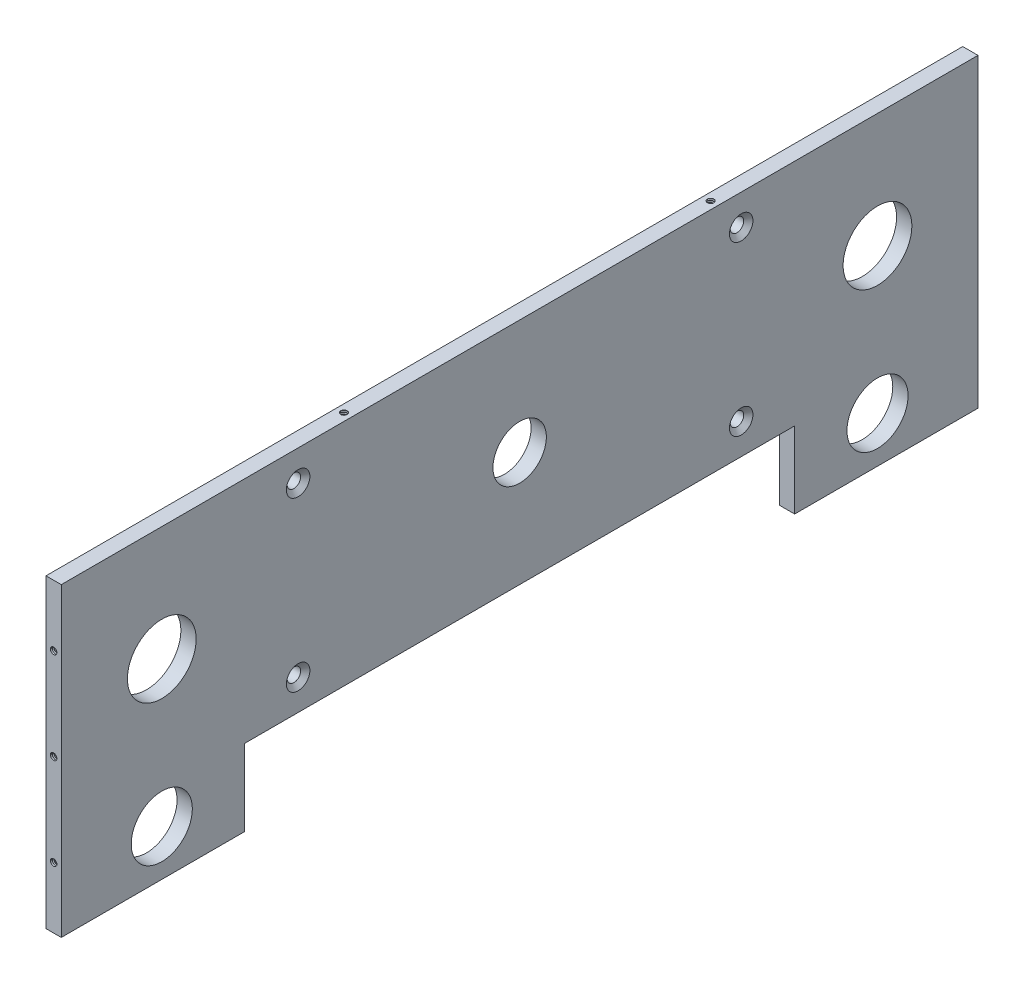
SolidWorks part; units mm, degrees
material "6061-T6 (SS)"
ref_plane "Front Plane" through (0, 0, 0) normal (0, 0, 1) x (1, 0, 0)
ref_plane "Top Plane" through (0, 0, 0) normal (0, 1, 0) x (1, 0, 0)
ref_plane "Right Plane" through (0, 0, 0) normal (1, 0, 0) x (0, 0, -1)
sketch "Sketch1" plane through (0, 0, 0) normal (1, 0, 0) x (0, 0, -1)
  line L1 (-190.5, 63.5) -> (190.5, 63.5)
  line L2 (-190.5, 63.5) -> (-190.5, -63.5)
  line L3 (-190.5, -63.5) -> (190.5, -63.5)
  line L4 (190.5, 63.5) -> (190.5, -63.5)
  line L5 (-190.5, 63.5) -> (190.5, -63.5) construction
  line L6 (-190.5, -63.5) -> (190.5, 63.5) construction
  point P0 (0, 0)
  dimension "D1" = 127
  dimension "D2" = 381
extrude "Boss-Extrude1" add sketch "Sketch1" along normal blind 6.35
sketch "Sketch2" plane through (6.35, 0, 0) normal (1, 0, 0) x (0, 0, -1)
  line L0 (-190.5, -63.5) -> (190.5, -63.5) construction
  line L1 (-148.7297, 15.875) -> (0, 15.875) construction
  line L2 (-74.3648, -34.925) -> (-74.3648, 15.875) construction
  line L3 (0, 15.875) -> (148.7297, 15.875) construction
  line L4 (74.3648, -34.925) -> (74.3648, 15.875) construction
  line L5 (190.5, 63.5) -> (-190.5, 63.5) construction
  line L6 (65.278, 53.34) -> (-56.642, 53.34) construction
  line L7 (65.278, 53.34) -> (65.278, -13.97) construction
  line L8 (65.278, -13.97) -> (-56.642, -13.97) construction
  line L9 (-56.642, 53.34) -> (-56.642, -13.97) construction
  line L10 (-190.5, -63.5) -> (190.5, -63.5) construction
  circle A1 centre (-148.7297, 15.875) radius 14.2875
  circle A2 centre (148.7297, 15.875) radius 14.2875
  circle A3 centre (-148.7297, 15.875) radius 38.1 construction
  circle A4 centre (0, 15.875) radius 38.1 construction
  circle A5 centre (148.7297, 15.875) radius 38.1 construction
  circle A6 centre (-74.3648, -34.925) radius 6.35 construction
  circle A7 centre (74.3648, -34.925) radius 6.35 construction
  circle A8 centre (-74.3648, 9.525) radius 6.35 construction
  circle A9 centre (74.3648, 9.525) radius 6.35 construction
  circle A11 centre (-148.7297, -44.4161) radius 12.7
  circle A12 centre (148.7297, -44.4161) radius 12.7
  circle A13 centre (0, 15.875) radius 11.1125
  point P11 (0, 0)
  dimension "D1" = 28.575
  dimension "D5" = 76.2
  dimension "D7" = 12.7
  dimension "D14" = 25.4
  dimension "D15" = 19.0839
  dimension "D17" = 25.4
  dimension "D20" = 22.225
  dimension "D21" = 28.575
  dimension "D2" = 79.375
  dimension "D3" = 148.7297
  dimension "D4" = 148.7297
  dimension "D6" = 0
  dimension "D8" = 28.575
  dimension "D9" = 44.45
  dimension "D10" = 56.642
  dimension "D11" = 121.92
  dimension "D12" = 10.16
  dimension "D13" = 49.53
  dimension "D16" = 148.7297
  dimension "D18" = 19.0839
  dimension "D19" = 148.7297
extrude "Cut-Extrude1" cut sketch "Sketch2" against normal through all
sketch "Sketch3" plane through (6.35, 0, 0) normal (1, 0, 0) x (0, 0, -1)
  line L0 (-184.404, 19.05) -> (-184.404, -19.05) construction
  line L1 (-190.5, 63.5) -> (-190.5, -63.5) construction
  point P2 (-184.404, 0)
  point P3 (-190.5, 0)
  dimension "D1" = 38.1
  dimension "D2" = 6.096
hole_wizard "CSK for #10 Flat Head Machine Screw (100)1" positions "Sketch7" profile "Sketch8" countersink size "#10" standard "ANSI Inch" end condition through all
sketch "Sketch7" plane through (6.35, 0, 0) normal (1, 0, 0) x (0, 0, -1)
  line L1 (190.5, 63.5) -> (-190.5, 63.5) construction
  point P15 (-92.075, 50.8)
  point P17 (92.075, 50.8)
  point P19 (-92.075, -19.05)
  point P21 (92.075, -19.05)
  dimension "D1" = 12.7
  dimension "D2" = 12.7
  dimension "D3" = 69.85
  dimension "D4" = 69.85
sketch "Sketch8" plane through (6.35, 50.8, 92.075) normal (0, 1, 0) x (0, 0, -1)
  line L0 (0, 0) -> (0, 6.35)
  line L1 (0, 6.35) -> (2.8067, 6.35)
  line L2 (2.8067, 6.35) -> (2.8067, 1.7477)
  line L3 (2.8067, 1.7477) -> (4.8895, 0)
  line L5 (4.8895, 0) -> (0, 0)
  line L6 (-2.8067, 1.7477) -> (-4.8895, 0) construction
  line L11 (0, -6.35) -> (0, 107.95) construction
  dimension "Thru Hole Dia." = 5.6134
  dimension "Thru Hole Depth" = 6.35
  dimension "Near C'Sink Dia." = 9.779
  dimension "Near C'Sink Angle" = 100
sketch "Sketch23" plane through (6.35, 0, 0) normal (1, 0, 0) x (0, 0, -1)
  line L0 (-114.3, -63.5) -> (-114.3, -31.75)
  line L1 (-190.5, -63.5) -> (190.5, -63.5) construction
  line L2 (-114.3, -31.75) -> (114.3, -31.75)
  line L3 (114.3, -31.75) -> (114.3, -63.5)
  line L4 (-190.5, 63.5) -> (-190.5, -63.5) construction
  line L5 (190.5, -63.5) -> (190.5, 63.5) construction
  line L6 (-114.3, -63.5) -> (114.3, -63.5)
  dimension "D1" = 31.75
  dimension "D2" = 76.2
  dimension "D3" = 76.2
extrude "Cut-Extrude6" cut sketch "Sketch23" against normal through all
sketch "Sketch24" plane through (0, 63.5, 0) normal (0, 1, 0) x (1, 0, 0)
  line L0 (6.35, 190.5) -> (0, 190.5) construction
  line L1 (6.35, -190.5) -> (0, -190.5) construction
  line L2 (6.35, 190.5) -> (6.35, -190.5) construction
  point P0 (3.175, 82.55)
  point P1 (3.175, -69.85)
  dimension "D1" = 107.95
  dimension "D2" = 120.65
  dimension "D3" = 3.175
hole_wizard "#36 (0.1065) Diameter Hole1" positions "Sketch25" profile "Sketch26" hole size "#36" standard "ANSI Inch"
sketch "Sketch25" plane through (0, 63.5, 0) normal (0, 1, 0) x (1, 0, 0)
  point P0 (3.175, 82.55)
  point P3 (3.175, -69.85)
sketch "Sketch26" plane through (3.175, 63.5, -82.55) normal (1, 0, 0) x (0, 0, 1)
  line L0 (0, 0) -> (0, 9.7027)
  line L1 (0, 9.7027) -> (1.3525, 8.89)
  line L2 (1.3525, 8.89) -> (1.3525, 0)
  line L5 (1.3525, 0) -> (0, 0)
  line L10 (0, 9.7027) -> (-1.3526, 8.89) construction
  line L11 (0, -6.35) -> (0, 107.95) construction
  dimension "Hole Dia." = 2.7051
  dimension "Hole Depth" = 8.89
  dimension "Drill Angle" = 118
thread "Thread1" pitch 0.7937 method cut profile "Thread Profile1" start angle 0, offset 0, length 6.35, pitch 0.7937, diameter 2.7051
ref_plane "Plane1" through (1.8225, 63.5, -82.55) normal (0, 0, 1) x (-1, 0, 0)
sketch "Thread Profile1" plane through (1.8225, 63.5, -82.55) normal (0, 0, 1) x (-1, 0, 0)
  line L0 (0, 0) -> (0, 0.7937) construction
  line L1 (0, 0) -> (0.4296, 0.248)
  line L2 (0.4296, 0.248) -> (0.4296, 0.3473)
  line L3 (0.4296, 0.3473) -> (0, 0.5953)
  line L4 (0.4296, 0.2977) -> (0, 0.2977) construction
  line L11 (0, 0) -> (0, 0.5953)
  point P2 (0, 0)
  dimension "Pitch" = 0.7937
  dimension "Profile_Angle" = 60
  dimension "Profile_Land" = 0.0992
  dimension "Profile_Height" = 0.4296
thread "Thread2" pitch 0.7937 method cut profile "Thread Profile2" start angle 0, offset 0, length 6.35, pitch 0.7937, diameter 2.7051
ref_plane "Plane2" through (1.8225, 63.5, 69.85) normal (0, 0, 1) x (-1, 0, 0)
sketch "Thread Profile2" plane through (1.8225, 63.5, 69.85) normal (0, 0, 1) x (-1, 0, 0)
  line L0 (0, 0) -> (0, 0.7937) construction
  line L1 (0, 0) -> (0.4296, 0.248)
  line L2 (0.4296, 0.248) -> (0.4296, 0.3473)
  line L3 (0.4296, 0.3473) -> (0, 0.5953)
  line L4 (0.4296, 0.2977) -> (0, 0.2977) construction
  line L11 (0, 0) -> (0, 0.5953)
  point P2 (0, 0)
  dimension "Pitch" = 0.7937
  dimension "Profile_Angle" = 60
  dimension "Profile_Land" = 0.0992
  dimension "Profile_Height" = 0.4296
sketch "Sketch27" plane through (0, 0, -190.5) normal (0, 0, -1) x (-1, 0, 0)
  line L0 (-6.35, 63.5) -> (0, 63.5) construction
  line L1 (-6.35, -63.5) -> (-6.35, 63.5) construction
  point P0 (-3.175, 38.1)
  point P1 (-3.175, 0)
  point P2 (-3.175, -38.1)
  dimension "D1" = 25.4
  dimension "D2" = 3.175
hole_wizard "#36 (0.1065) Diameter Hole2" positions "Sketch28" profile "Sketch29" hole size "#36" standard "ANSI Inch"
sketch "Sketch28" plane through (0, 0, -190.5) normal (0, 0, -1) x (-1, 0, 0)
  point P0 (-3.175, 38.1)
  point P3 (-3.175, 0)
  point P6 (-3.175, -38.1)
sketch "Sketch29" plane through (3.175, 38.1, -190.5) normal (1, 0, 0) x (0, 1, 0)
  line L0 (0, 0) -> (0, 9.7027)
  line L1 (0, 9.7027) -> (1.3525, 8.89)
  line L2 (1.3525, 8.89) -> (1.3525, 0)
  line L5 (1.3525, 0) -> (0, 0)
  line L10 (0, 9.7027) -> (-1.3526, 8.89) construction
  line L11 (0, -6.35) -> (0, 107.95) construction
  dimension "Hole Dia." = 2.7051
  dimension "Hole Depth" = 8.89
  dimension "Drill Angle" = 118
thread "Thread3" pitch 0.7937 method cut profile "Thread Profile3" start angle 0, offset 0, length 6.35, pitch 0.7937, diameter 2.7051
ref_plane "Plane3" through (4.5275, 38.1, -190.5) normal (0, -1, 0) x (1, 0, 0)
sketch "Thread Profile3" plane through (4.5275, 38.1, -190.5) normal (0, -1, 0) x (1, 0, 0)
  line L0 (0, 0) -> (0, 0.7937) construction
  line L1 (0, 0) -> (0.4296, 0.248)
  line L2 (0.4296, 0.248) -> (0.4296, 0.3473)
  line L3 (0.4296, 0.3473) -> (0, 0.5953)
  line L4 (0.4296, 0.2977) -> (0, 0.2977) construction
  line L11 (0, 0) -> (0, 0.5953)
  point P2 (0, 0)
  dimension "Pitch" = 0.7937
  dimension "Profile_Angle" = 60
  dimension "Profile_Land" = 0.0992
  dimension "Profile_Height" = 0.4296
thread "Thread4" pitch 0.7937 method cut profile "Thread Profile4" start angle 0, offset 0, length 6.35, pitch 0.7937, diameter 2.7051
ref_plane "Plane4" through (4.5275, 0, -190.5) normal (0, -1, 0) x (1, 0, 0)
sketch "Thread Profile4" plane through (4.5275, 0, -190.5) normal (0, -1, 0) x (1, 0, 0)
  line L0 (0, 0) -> (0, 0.7937) construction
  line L1 (0, 0) -> (0.4296, 0.248)
  line L2 (0.4296, 0.248) -> (0.4296, 0.3473)
  line L3 (0.4296, 0.3473) -> (0, 0.5953)
  line L4 (0.4296, 0.2977) -> (0, 0.2977) construction
  line L11 (0, 0) -> (0, 0.5953)
  point P2 (0, 0)
  dimension "Pitch" = 0.7937
  dimension "Profile_Angle" = 60
  dimension "Profile_Land" = 0.0992
  dimension "Profile_Height" = 0.4296
thread "Thread5" pitch 0.7937 method cut profile "Thread Profile5" start angle 0, offset 0, length 6.35, pitch 0.7937, diameter 2.7051
ref_plane "Plane5" through (4.5275, -38.1, -190.5) normal (0, -1, 0) x (1, 0, 0)
sketch "Thread Profile5" plane through (4.5275, -38.1, -190.5) normal (0, -1, 0) x (1, 0, 0)
  line L0 (0, 0) -> (0, 0.7937) construction
  line L1 (0, 0) -> (0.4296, 0.248)
  line L2 (0.4296, 0.248) -> (0.4296, 0.3473)
  line L3 (0.4296, 0.3473) -> (0, 0.5953)
  line L4 (0.4296, 0.2977) -> (0, 0.2977) construction
  line L11 (0, 0) -> (0, 0.5953)
  point P2 (0, 0)
  dimension "Pitch" = 0.7937
  dimension "Profile_Angle" = 60
  dimension "Profile_Land" = 0.0992
  dimension "Profile_Height" = 0.4296
sketch "Sketch36" plane through (0, 0, 190.5) normal (0, 0, 1) x (1, 0, 0)
  line L0 (6.35, 63.5) -> (6.35, -63.5) construction
  point P0 (3.175, 38.1)
  point P1 (3.175, 0)
  point P2 (3.175, -38.1)
  dimension "D1" = 25.4
  dimension "D2" = 3.175
  dimension "D3" = 38.1
  dimension "D4" = 38.1
hole_wizard "#36 (0.1065) Diameter Hole3" positions "Sketch37" profile "Sketch38" hole size "#36" standard "ANSI Inch"
sketch "Sketch37" plane through (0, 0, 190.5) normal (0, 0, 1) x (1, 0, 0)
  point P0 (3.175, 38.1)
  point P3 (3.175, 0)
  point P6 (3.175, -38.1)
sketch "Sketch38" plane through (3.175, 38.1, 190.5) normal (1, 0, 0) x (0, -1, 0)
  line L0 (0, 0) -> (0, 9.7027)
  line L1 (0, 9.7027) -> (1.3525, 8.89)
  line L2 (1.3525, 8.89) -> (1.3525, 0)
  line L5 (1.3525, 0) -> (0, 0)
  line L10 (0, 9.7027) -> (-1.3525, 8.89) construction
  line L11 (0, -6.35) -> (0, 107.95) construction
  dimension "Hole Dia." = 2.7051
  dimension "Hole Depth" = 8.89
  dimension "Drill Angle" = 118
thread "Thread6" pitch 0.7937 method cut profile "Thread Profile6" start angle 0, offset 0, length 6.35, pitch 0.7937, diameter 2.7051
ref_plane "Plane6" through (1.8225, 38.1, 190.5) normal (0, -1, 0) x (-1, 0, 0)
sketch "Thread Profile6" plane through (1.8225, 38.1, 190.5) normal (0, -1, 0) x (-1, 0, 0)
  line L0 (0, 0) -> (0, 0.7937) construction
  line L1 (0, 0) -> (0.4296, 0.248)
  line L2 (0.4296, 0.248) -> (0.4296, 0.3473)
  line L3 (0.4296, 0.3473) -> (0, 0.5953)
  line L4 (0.4296, 0.2977) -> (0, 0.2977) construction
  line L11 (0, 0) -> (0, 0.5953)
  point P2 (0, 0)
  dimension "Pitch" = 0.7937
  dimension "Profile_Angle" = 60
  dimension "Profile_Land" = 0.0992
  dimension "Profile_Height" = 0.4296
thread "Thread7" pitch 0.7937 method cut profile "Thread Profile7" start angle 0, offset 0, length 6.35, pitch 0.7937, diameter 2.7051
ref_plane "Plane7" through (1.8225, 0, 190.5) normal (0, -1, 0) x (-1, 0, 0)
sketch "Thread Profile7" plane through (1.8225, 0, 190.5) normal (0, -1, 0) x (-1, 0, 0)
  line L0 (0, 0) -> (0, 0.7937) construction
  line L1 (0, 0) -> (0.4296, 0.248)
  line L2 (0.4296, 0.248) -> (0.4296, 0.3473)
  line L3 (0.4296, 0.3473) -> (0, 0.5953)
  line L4 (0.4296, 0.2977) -> (0, 0.2977) construction
  line L11 (0, 0) -> (0, 0.5953)
  point P2 (0, 0)
  dimension "Pitch" = 0.7937
  dimension "Profile_Angle" = 60
  dimension "Profile_Land" = 0.0992
  dimension "Profile_Height" = 0.4296
thread "Thread8" pitch 0.7937 method cut profile "Thread Profile8" start angle 0, offset 0, length 6.35, pitch 0.7937, diameter 2.7051
ref_plane "Plane8" through (1.8225, -38.1, 190.5) normal (0, -1, 0) x (-1, 0, 0)
sketch "Thread Profile8" plane through (1.8225, -38.1, 190.5) normal (0, -1, 0) x (-1, 0, 0)
  line L0 (0, 0) -> (0, 0.7937) construction
  line L1 (0, 0) -> (0.4296, 0.248)
  line L2 (0.4296, 0.248) -> (0.4296, 0.3473)
  line L3 (0.4296, 0.3473) -> (0, 0.5953)
  line L4 (0.4296, 0.2977) -> (0, 0.2977) construction
  line L11 (0, 0) -> (0, 0.5953)
  point P2 (0, 0)
  dimension "Pitch" = 0.7937
  dimension "Profile_Angle" = 60
  dimension "Profile_Land" = 0.0992
  dimension "Profile_Height" = 0.4296
